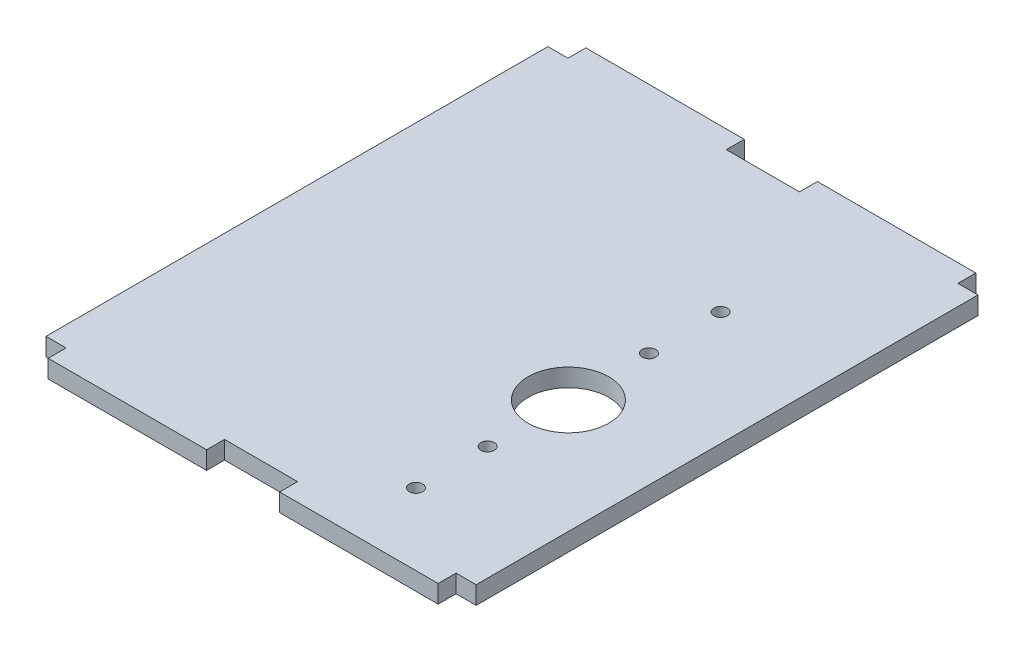
SolidWorks part; units mm, degrees
ref_plane "Front Plane" through (0, 0, 0) normal (0, 0, 1) x (1, 0, 0)
ref_plane "Top Plane" through (0, 0, 0) normal (0, 1, 0) x (1, 0, 0)
ref_plane "Right Plane" through (0, 0, 0) normal (1, 0, 0) x (0, 0, -1)
sketch "Sketch1" plane through (0, 0, 0) normal (0, 1, 0) x (1, 0, 0)
  line L1 (0, 0) -> (304.8, 0)
  line L2 (0, 0) -> (0, 355.6)
  line L3 (0, 355.6) -> (304.8, 355.6)
  line L4 (304.8, 0) -> (304.8, 355.6)
  dimension "D1" = 355.6
  dimension "D2" = 304.8
extrude "Boss-Extrude1" add sketch "Sketch1" along normal blind 12.7
sketch "Sketch2" plane through (0, 0, 0) normal (0, -1, 0) x (1, 0, 0)
  line L0 (0, 0) -> (304.8, 0) construction
  line L1 (0, -355.6) -> (0, 0) construction
  circle A0 centre (224.028, -38.1) radius 4.7625
  circle A1 centre (224.028, -88.9) radius 4.7625
  circle A2 centre (224.028, -203.2) radius 4.7625
  circle A3 centre (224.028, -254) radius 4.7625
  dimension "D3" = 88.9
  dimension "D6" = 9.525
  dimension "D1" = 38.1
  dimension "D2" = 224.028
  dimension "D4" = 203.2
  dimension "D5" = 254
  dimension "D7" = 224.028
  dimension "D8" = 224.028
  dimension "D9" = 224.028
extrude "Cut-Extrude1" cut sketch "Sketch2" against normal blind 12.7
sketch "Sketch3" plane through (0, 12.7, 0) normal (0, 1, 0) x (1, 0, 0)
  line L0 (152.4, 355.6) -> (152.4, 250.206) construction
  line L1 (0, 177.8) -> (22.2548, 177.8) construction
  line L2 (14.224, 355.6) -> (126.492, 355.6)
  line L3 (14.224, 355.6) -> (14.224, 368.3)
  line L4 (0, 355.6) -> (0, 0)
  line L5 (0, 0) -> (304.8, 0)
  line L6 (304.8, 0) -> (304.8, 355.6)
  line L7 (304.8, 355.6) -> (0, 355.6)
  line L8 (0, 355.6) -> (0, 0) construction
  line L9 (0, 0) -> (304.8, 0) construction
  line L10 (304.8, 0) -> (304.8, 355.6) construction
  line L11 (304.8, 355.6) -> (0, 355.6) construction
  line L12 (14.224, 368.3) -> (126.492, 368.3)
  line L13 (126.492, 355.6) -> (126.492, 368.3)
  line L14 (290.576, 368.3) -> (178.308, 368.3)
  line L15 (178.308, 355.6) -> (178.308, 368.3)
  line L16 (290.576, 355.6) -> (178.308, 355.6)
  line L17 (290.576, 355.6) -> (290.576, 368.3)
  line L18 (290.576, 0) -> (290.576, -12.7)
  line L19 (290.576, 0) -> (178.308, 0)
  line L20 (178.308, 0) -> (178.308, -12.7)
  line L21 (290.576, -12.7) -> (178.308, -12.7)
  line L22 (14.224, -12.7) -> (126.492, -12.7)
  line L23 (126.492, 0) -> (126.492, -12.7)
  line L24 (14.224, 0) -> (126.492, 0)
  line L25 (14.224, 0) -> (14.224, -12.7)
  point P24 (190.5, 250.206)
  dimension "D2" = 25.908
  dimension "D3" = 112.268
  dimension "D4" = 12.7
  dimension "D1" = 0
extrude "Boss-Extrude2" add sketch "Sketch3" against normal blind 12.7
sketch "Sketch4" plane through (0, 0, 0) normal (0, -1, 0) x (1, 0, 0)
  line L20 (0, 0) -> (0, -355.6)
  line L21 (0, -355.6) -> (14.224, -355.6)
  line L22 (14.224, -355.6) -> (14.224, -368.3)
  line L23 (14.224, -368.3) -> (126.492, -368.3)
  line L24 (126.492, -368.3) -> (126.492, -355.6)
  line L25 (126.492, -355.6) -> (178.308, -355.6)
  line L26 (178.308, -355.6) -> (178.308, -368.3)
  line L27 (178.308, -368.3) -> (290.576, -368.3)
  line L28 (290.576, -368.3) -> (290.576, -355.6)
  line L29 (290.576, -355.6) -> (304.8, -355.6)
  line L30 (304.8, -355.6) -> (304.8, 0)
  line L31 (304.8, 0) -> (290.576, 0)
  line L32 (290.576, 0) -> (290.576, 12.7)
  line L33 (290.576, 12.7) -> (178.308, 12.7)
  line L34 (178.308, 12.7) -> (178.308, 0)
  line L35 (178.308, 0) -> (126.492, 0)
  line L36 (126.492, 0) -> (126.492, 12.7)
  line L37 (126.492, 12.7) -> (14.224, 12.7)
  line L38 (14.224, 12.7) -> (14.224, 0)
  line L39 (14.224, 0) -> (0, 0)
  line L40 (0, 0) -> (0, -355.6)
  line L41 (0, -355.6) -> (14.224, -355.6)
  line L42 (14.224, -355.6) -> (14.224, -368.3)
  line L43 (14.224, -368.3) -> (126.492, -368.3)
  line L44 (126.492, -368.3) -> (126.492, -355.6)
  line L45 (126.492, -355.6) -> (178.308, -355.6)
  line L46 (178.308, -355.6) -> (178.308, -368.3)
  line L47 (178.308, -368.3) -> (290.576, -368.3)
  line L48 (290.576, -368.3) -> (290.576, -355.6)
  line L49 (290.576, -355.6) -> (304.8, -355.6)
  line L50 (304.8, -355.6) -> (304.8, 0)
  line L51 (304.8, 0) -> (290.576, 0)
  line L52 (290.576, 0) -> (290.576, 12.7)
  line L53 (290.576, 12.7) -> (178.308, 12.7)
  line L54 (178.308, 12.7) -> (178.308, 0)
  line L55 (178.308, 0) -> (126.492, 0)
  line L56 (126.492, 0) -> (126.492, 12.7)
  line L57 (126.492, 12.7) -> (14.224, 12.7)
  line L58 (14.224, 12.7) -> (14.224, 0)
  line L59 (14.224, 0) -> (0, 0)
  circle A0 centre (224.1175, -146.05) radius 28.575
  circle A5 centre (224.028, -203.2) radius 4.7625 construction
  circle A6 centre (224.028, -88.9) radius 4.7625 construction
  point P6 (0, 0)
  point P8 (0, 0)
  point P14 (224.028, -88.9)
  dimension "D2" = 57.15
  dimension "D3" = 109.5375
  dimension "D4" = 57.15
  dimension "D1" = 0
extrude "Cut-Extrude2" cut sketch "Sketch4" against normal blind 12.7 contours A0
